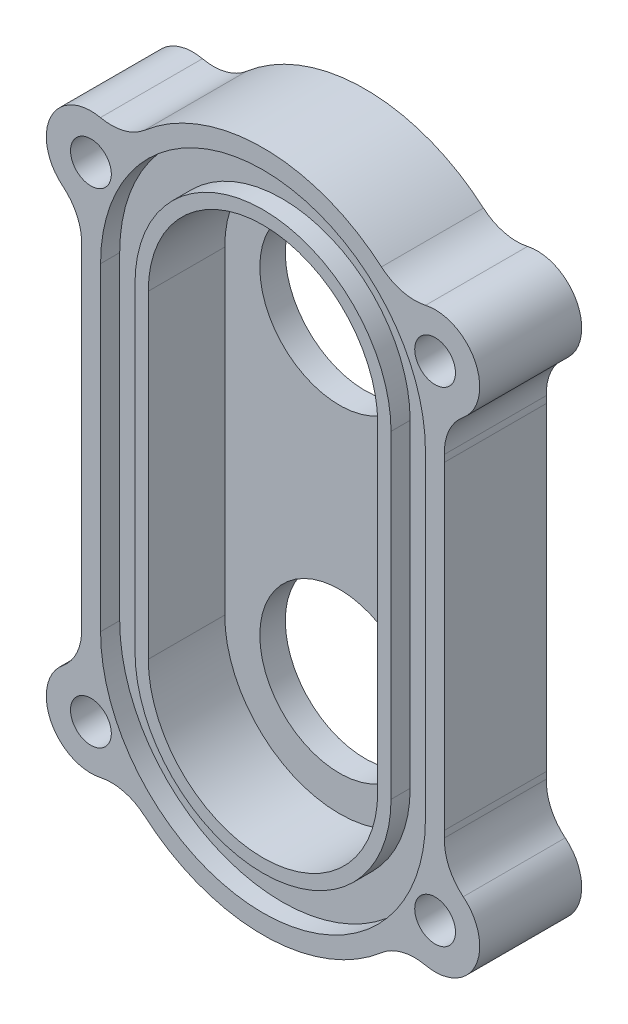
SolidWorks part; units mm, degrees
material "3.1325 (EN-AW 2017A)"
ref_plane "正面" through (0, 0, 0) normal (0, 0, 1) x (1, 0, 0)
ref_plane "平面" through (0, 0, 0) normal (0, 1, 0) x (1, 0, 0)
ref_plane "右側面" through (0, 0, 0) normal (1, 0, 0) x (0, 0, -1)
sketch "ｽｹｯﾁ1" plane through (0, 0, 0) normal (0, 0, 1) x (1, 0, 0)
  line L0 (0, 0) -> (81693.4409, 0) construction
  line L1 (-9, 12.5) -> (-9, -12.5)
  line L2 (-14.2423, 12.5) -> (-14.2423, -12.5)
  line L3 (14.2423, 12.5) -> (14.2423, -12.5)
  line L5 (0, 0) -> (0, -81693.4409) construction
  line L7 (9, 12.5) -> (9, -12.5)
  line L8 (-10.0423, 12.5) -> (-10.0423, -12.5)
  line L9 (10.0423, 12.5) -> (10.0423, -12.5)
  line L10 (-12.7423, 12.5) -> (-12.7423, -12.5)
  line L11 (12.7423, 12.5) -> (12.7423, -12.5)
  circle A0 centre (0, 12.5) radius 6.25
  arc A1 (9, 12.5) -> (-9, 12.5) centre (0, 12.5) ccw
  arc A2 (9, -12.5) -> (-9, -12.5) centre (0, -12.5) cw
  circle A3 centre (0, -12.5) radius 6.25
  arc A4 (14.2423, 12.5) -> (14.2324, 13.0303) centre (0, 12.5) ccw
  arc A5 (14.2423, -12.5) -> (14.2324, -13.0303) centre (0, -12.5) cw
  arc A7 (-12.7529, 22.4193) -> (-15.7071, 16.2837) centre (-13.5, 19) ccw
  arc A8 (10.0423, 12.5) -> (-10.0423, 12.5) centre (0, 12.5) ccw
  arc A9 (10.0423, -12.5) -> (-10.0423, -12.5) centre (0, -12.5) cw
  arc A10 (12.7423, 12.5) -> (-12.7423, 12.5) centre (0, 12.5) ccw
  arc A11 (12.7423, -12.5) -> (-12.7423, -12.5) centre (0, -12.5) cw
  arc A12 (-14.2324, 13.0303) -> (-15.7071, 16.2837) centre (-18.2296, 13.1793) ccw
  arc A13 (-12.7529, 22.4193) -> (-9.29, 23.2953) centre (-11.8991, 26.3272) ccw
  arc A14 (12.7529, 22.4193) -> (9.29, 23.2953) centre (11.8991, 26.3272) cw
  arc A15 (12.7529, 22.4193) -> (15.7071, 16.2837) centre (13.5, 19) cw
  arc A16 (14.2324, 13.0303) -> (15.7071, 16.2837) centre (18.2296, 13.1793) cw
  arc A17 (14.2324, -13.0303) -> (15.7071, -16.2837) centre (18.2296, -13.1793) ccw
  arc A18 (12.7529, -22.4193) -> (15.7071, -16.2837) centre (13.5, -19) ccw
  arc A19 (12.7529, -22.4193) -> (9.29, -23.2953) centre (11.8991, -26.3272) ccw
  arc A20 (-12.7529, -22.4193) -> (-9.29, -23.2953) centre (-11.8991, -26.3272) cw
  arc A21 (-12.7529, -22.4193) -> (-15.7071, -16.2837) centre (-13.5, -19) cw
  arc A22 (-14.2324, -13.0303) -> (-15.7071, -16.2837) centre (-18.2296, -13.1793) cw
  arc A23 (-14.2324, 13.0303) -> (-14.2423, 12.5) centre (0, 12.5) ccw
  arc A24 (14.2423, 12.5) -> (-14.2423, 12.5) centre (0, 12.5) ccw construction
  arc A25 (9.29, 23.2953) -> (-9.29, 23.2953) centre (0, 12.5) ccw
  arc A26 (-14.2324, -13.0303) -> (-14.2423, -12.5) centre (0, -12.5) cw
  arc A27 (14.2423, -12.5) -> (-14.2423, -12.5) centre (0, -12.5) cw construction
  arc A28 (9.29, -23.2953) -> (-9.29, -23.2953) centre (0, -12.5) cw
  point P66 (0, 0)
  dimension "D1" = 12.5
  dimension "D2" = 18
  dimension "D6" = 20.0845
  dimension "D8" = 7
  dimension "D11" = 8
  dimension "D3" = 25
  dimension "D7" = 2.7
  dimension "D4" = 1.5
  dimension "D9" = 27
  dimension "D5" = 38
extrude "ﾎﾞｽ - 押し出し1" add sketch "ｽｹｯﾁ1" along normal blind 8 contours A4 A16 A15 A14 A25 A13 A7 A12 A23 L2 A26 A22 A21 A20 A28 A19 A18 A17 A5 L3 | A0 | A3
extrude "ｶｯﾄ - 押し出し1" cut sketch "ｽｹｯﾁ1<3>" along normal through all from offset 2 contours A1 L1 A2 L7
sketch "ｽｹｯﾁ1<3>" plane through (0, 0, 0) normal (0, 0, 1) x (1, 0, 0) same geometry as "ｽｹｯﾁ1"
extrude "ｶｯﾄ - 押し出し4" cut sketch "ｽｹｯﾁ1<6>" against normal blind 1.5 from surface contours A11 L11 A10 L10 L9 A9 L8 A8 region at (0, 24.6767, 0) starting at face at (0, 0, 8)
sketch "ｽｹｯﾁ1<6>" plane through (0, 0, 0) normal (0, 0, 1) x (1, 0, 0) same geometry as "ｽｹｯﾁ1"
hole_wizard "M3 すきま穴2" positions "3Dｽｹｯﾁ3" profile "ｽｹｯﾁ4" hole size "M3" standard "JIS" end condition through all
sketch3d "3Dｽｹｯﾁ3"
  point P0 (-13.5, 19, 0)
  point P2 (-13.5, -19, 0)
  point P4 (13.5, -19, 0)
  point P6 (13.5, 19, 0)
sketch "ｽｹｯﾁ4" plane through (-13.5, 19, 0) normal (1, 0, 0) x (0, 1, 0)
  line L0 (0, 0) -> (0, 8)
  line L1 (0, 8) -> (1.6, 8)
  line L2 (1.6, 8) -> (1.6, 0)
  line L5 (1.6, 0) -> (0, 0)
  line L11 (0, -6.35) -> (0, 107.95) construction
  dimension "通し穴の直径" = 3.2
  dimension "通し穴の深さ" = 8
sketch "ｽｹｯﾁ5" plane through (0, 0, 8) normal (0, 0, 1) x (1, 0, 0)
  line L4 (18.2423, -12.5) -> (18.2423, 12.5)
  line L5 (-18.2423, 12.5) -> (-18.2423, -12.5)
  line L6 (18.2423, -12.5) -> (18.2423, 12.5)
  line L7 (-18.2423, 12.5) -> (-18.2423, -12.5)
  arc A36 (18.2423, 12.5) -> (18.2296, 13.1793) centre (0, 12.5) ccw
  arc A37 (18.2296, 13.1793) -> (11.8991, 26.3272) centre (13.5, 19) ccw
  arc A38 (11.8991, 26.3272) -> (-11.8991, 26.3272) centre (0, 12.5) ccw
  arc A39 (-11.8991, 26.3272) -> (-18.2296, 13.1793) centre (-13.5, 19) ccw
  arc A40 (-18.2296, 13.1793) -> (-18.2423, 12.5) centre (0, 12.5) ccw
  arc A41 (-18.2423, -12.5) -> (-18.2296, -13.1793) centre (0, -12.5) ccw
  arc A42 (-18.2296, -13.1793) -> (-11.8991, -26.3272) centre (-13.5, -19) ccw
  arc A43 (-11.8991, -26.3272) -> (11.8991, -26.3272) centre (0, -12.5) ccw
  arc A44 (11.8991, -26.3272) -> (18.2296, -13.1793) centre (13.5, -19) ccw
  arc A45 (18.2296, -13.1793) -> (18.2423, -12.5) centre (0, -12.5) ccw
  arc A46 (18.2423, 12.5) -> (18.2296, 13.1793) centre (0, 12.5) ccw
  arc A47 (18.2296, 13.1793) -> (11.8991, 26.3272) centre (13.5, 19) ccw
  arc A48 (11.8991, 26.3272) -> (-11.8991, 26.3272) centre (0, 12.5) ccw
  arc A49 (-11.8991, 26.3272) -> (-18.2296, 13.1793) centre (-13.5, 19) ccw
  arc A50 (-18.2296, 13.1793) -> (-18.2423, 12.5) centre (0, 12.5) ccw
  arc A51 (-18.2423, -12.5) -> (-18.2296, -13.1793) centre (0, -12.5) ccw
  arc A52 (-18.2296, -13.1793) -> (-11.8991, -26.3272) centre (-13.5, -19) ccw
  arc A53 (-11.8991, -26.3272) -> (11.8991, -26.3272) centre (0, -12.5) ccw
  arc A54 (11.8991, -26.3272) -> (18.2296, -13.1793) centre (13.5, -19) ccw
  arc A55 (18.2296, -13.1793) -> (18.2423, -12.5) centre (0, -12.5) ccw
  dimension "D1" = 4
equation "\"D6@ｽｹｯﾁ1\" = ( \"オーリング周長\" - 50 ) / pi"
equation "\"オーリング内径35.5mm\"= 36"
equation "\"オーリング周長\" = \"オーリング内径35.5mm\" * pi"
